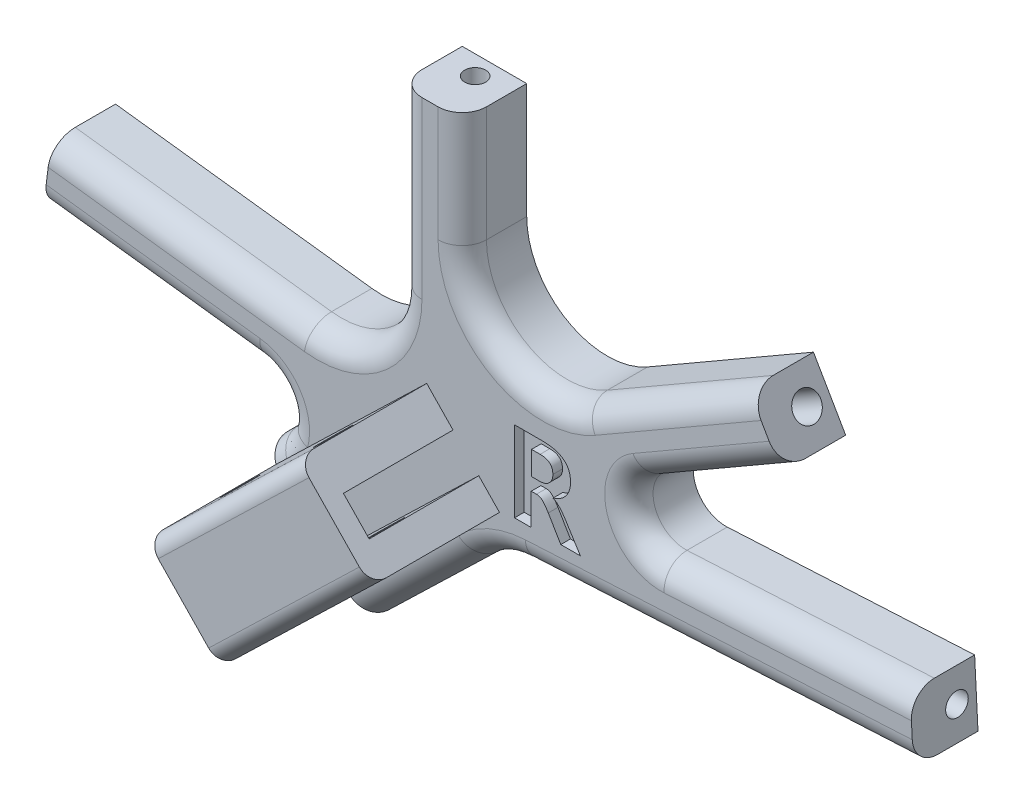
SolidWorks part; units mm, degrees
ref_plane "前基準面" through (0, 0, 0) normal (0, 0, 1) x (1, 0, 0)
ref_plane "上基準面" through (0, 0, 0) normal (0, 1, 0) x (1, 0, 0)
ref_plane "右基準面" through (0, 0, 0) normal (1, 0, 0) x (0, 0, -1)
sketch "草圖1" plane through (0, 0, 0) normal (0, 0, 1) x (1, 0, 0)
  line L0 (-27, 0) -> (-10.6362, 0) construction
  line L1 (-27, 3.1712) -> (-9.5687, 1.0309)
  line L2 (1.1225, -1.1562) -> (27, 0.2)
  line L3 (-27, 3.1712) -> (-26.5125, 7.1414)
  line L4 (-26.5125, 7.1414) -> (-5, 4.5)
  line L5 (3.1228, 2.9541) -> (26.7907, 4.1945)
  line L6 (26.7907, 4.1945) -> (27, 0.2)
  line L7 (-1, 5.1927) -> (16.7907, 15.4641)
  line L8 (16.7907, 15.4641) -> (18.7907, 12)
  line L9 (18.7907, 12) -> (3.1228, 2.9541)
  line L10 (-5, 4.5) -> (-5, 21)
  line L11 (-5, 21) -> (-1, 21)
  line L12 (-1, 21) -> (-1, 5.1927)
  line L13 (-9.5687, 1.0309) -> (-13.2519, -2.5259)
  line L14 (-13.2519, -2.5259) -> (-7, -9)
  line L15 (-7, -9) -> (1.1225, -1.1562)
  line L17 (2.3198, 0) -> (27, 0) construction
  point P19 (-10.6362, 0)
  dimension "D1" = 54
  dimension "D2" = 27
  dimension "D3" = 7
  dimension "D4" = 3
  dimension "D5" = 90
  dimension "D6" = 4
  dimension "D7" = 4
  dimension "D8" = 4.5
  dimension "D9" = 4
  dimension "D10" = 30
  dimension "D11" = 8
  dimension "D12" = 12
  dimension "D13" = 4
  dimension "D14" = 22
  dimension "D15" = 136
  dimension "D16" = 90
  dimension "D17" = 9
  dimension "D18" = 20
  dimension "D19" = 16.5
  dimension "D20" = 0.2
  dimension "D21" = 9
  dimension "D22" = 60
extrude "填料-伸長1" add sketch "草圖1" along normal blind 4
fillet "圓角1" radius 5 3 edges at (1.1225, -1.1562, 2) (-1, 5.1927, 2) (-5, 4.5, 2)
fillet "圓角2" radius 2 2 edges at (-9.5687, 1.0309, 2) (3.1228, 2.9541, 2)
sketch "草圖2" plane through (0, 0, 4) normal (0, 0, 1) x (1, 0, 0)
  line L1 (-8.042, -7.921) -> (1.3094, 1.1096)
  line L3 (1.3094, 1.1096) -> (-3.2058, 5.7853)
  line L4 (-3.2058, 5.7853) -> (-12.5573, -3.2453)
  line L5 (-12.5573, -3.2453) -> (-8.042, -7.921)
  line L6 (-7, -9) -> (-0.2222, -2.4548) construction
  dimension "D1" = 90
  dimension "D2" = 6.5
  dimension "D3" = 13
  dimension "D4" = 1.5
extrude "填料-伸長2" add sketch "草圖2" along normal blind 8
sketch "草圖3" plane through (-4.4379, 4.5955, 0) normal (-0.6947, 0.7193, 0) x (0, 0, 1)
  line L0 (12, 1.7127) -> (12, -11.2873) construction
  line L1 (12, -11.2873) -> (4, -11.2873) construction
  circle A0 centre (8, -8.7873) radius 1
  circle A2 centre (8, -0.7873) radius 1
  dimension "D5" = 2
  dimension "D7" = 2
  dimension "D1" = 4
  dimension "D2" = 2.5
  dimension "D3" = 8
extrude "除料-伸長1" cut sketch "草圖3" against normal up to next
fillet "圓角4" radius 1.5 15 edges at (-3.6111, -5.7274, 4) (1.2573, -1.4662, 4) (19.1163, 3.7923, 4) (9.4196, 4.8194, 4) (11.6453, 12.4934, 4) (1.5, 9.5228, 4) (-5, 15.5757, 4) (-6.6869, 6.4067, 4) (-12.9184, -2.2039, 4) (-12.0776, 0.1915, 4) (14.9947, -0.4292, 4) (14.564, 9.5597, 4) (-1, 17.4265, 4) (-18.5609, 6.1651, 4) (-20.3653, 2.3566, 4)
sketch "草圖5" plane through (26.9365, 1.4117, 0) normal (0.9986, 0.0523, 0) x (0, 0, -1)
  line L0 (0, 2.7867) -> (-2.5, 2.7867) construction
  line L1 (0, -1.2133) -> (0, 2.7867) construction
  circle A0 centre (-1.2, 0.7867) radius 0.7
  dimension "D3" = 1.4
  dimension "D1" = 2
  dimension "D2" = 1.2
extrude "除料-伸長3" cut sketch "草圖5" against normal blind 20
sketch "草圖6" plane through (19.2891, 11.1366, 0) normal (0.866, 0.5, 0) x (0, 0, -1)
  line L0 (0, 4.997) -> (-2.5, 4.997) construction
  line L1 (0, 0.997) -> (0, 4.997) construction
  circle A0 centre (-1.4, 2.997) radius 0.85
  dimension "D2" = 1.7
  dimension "D1" = 2
  dimension "D3" = 1.4
extrude "除料-伸長4" cut sketch "草圖6" against normal blind 20
sketch "草圖7" plane through (0, 21, 0) normal (0, 1, 0) x (1, 0, 0)
  line L0 (-1, -2.5) -> (-1, 0) construction
  line L1 (-1, 0) -> (-5, 0) construction
  circle A0 centre (-3, -1.2) radius 0.65
  dimension "D2" = 1.3
  dimension "D1" = 2
  dimension "D3" = 1.2
extrude "除料-伸長5" cut sketch "草圖7" against normal blind 20
sketch "草圖8" plane through (-26.9826, 3.313, 0) normal (-0.9925, 0.1219, 0) x (0, 0, 1)
  line L0 (2.5, 3.8571) -> (0, 3.8571) construction
  line L1 (0, 3.8571) -> (0, -0.1429) construction
  circle A0 centre (1.2, 1.8571) radius 0.65
  dimension "D2" = 1.3
  dimension "D1" = 2
  dimension "D3" = 1.2
extrude "除料-伸長6" cut sketch "草圖8" against normal blind 20
sketch "草圖9" plane through (-8.1194, -7.8408, 0) normal (-0.7193, -0.6947, 0) x (0, 0, 1)
  line L0 (12, -0.1114) -> (4, -0.1114) construction
  line L1 (10.8, 4.0386) -> (4, 4.0386)
  line L2 (10.8, 4.0386) -> (10.8, 1.7386)
  line L3 (10.8, 1.7386) -> (4, 1.7386)
  line L4 (4, 4.0386) -> (4, 1.7386)
  line L5 (10.8, 4.0386) -> (4, 1.7386) construction
  line L6 (10.8, 1.7386) -> (4, 4.0386) construction
  line L7 (12, 6.3886) -> (12, -0.1114) construction
  point P0 (7.4, 2.8886)
  dimension "D1" = 2.3
  dimension "D2" = 3
  dimension "D3" = 6.8
  dimension "D4" = 4.6
extrude "除料-伸長7" cut sketch "草圖9" against normal blind 14
sketch "草圖10" plane through (0.0774, -0.0802, 0) normal (0.6947, -0.7193, 0) x (0.7193, 0.6947, 0)
  line L1 (-10.5373, 10.75) -> (-12.0373, 10.75)
  line L2 (-10.5373, 10.75) -> (-10.5373, 5.25)
  line L3 (-10.5373, 5.25) -> (-12.0373, 5.25)
  line L4 (-12.0373, 10.75) -> (-12.0373, 5.25)
  line L5 (-10.5373, 10.75) -> (-12.0373, 5.25) construction
  line L6 (-10.5373, 5.25) -> (-12.0373, 10.75) construction
  line L7 (-11.2873, 12) -> (-11.2873, 4) construction
  point P0 (-11.2873, 8)
  dimension "D1" = 1.5
  dimension "D2" = 5.5
extrude "除料-伸長8" cut sketch "草圖10" against normal up to next
fillet "圓角5" radius 3 2 edges at (-8.145, -6.7346, 5.25) (-8.145, -6.7346, 10.75)
fillet "圓角6" radius 1 2 edges at (-3.3663, -3.4057, 12) (-7.8816, 1.27, 12)
sketch "草圖11" plane through (0, 0, 4) normal (0, 0, 1) x (1, 0, 0)
  text T0 "R" font "Microsoft YaHei UI" height 5
extrude "除料-伸長9" cut sketch "草圖11" against normal blind 0.6
